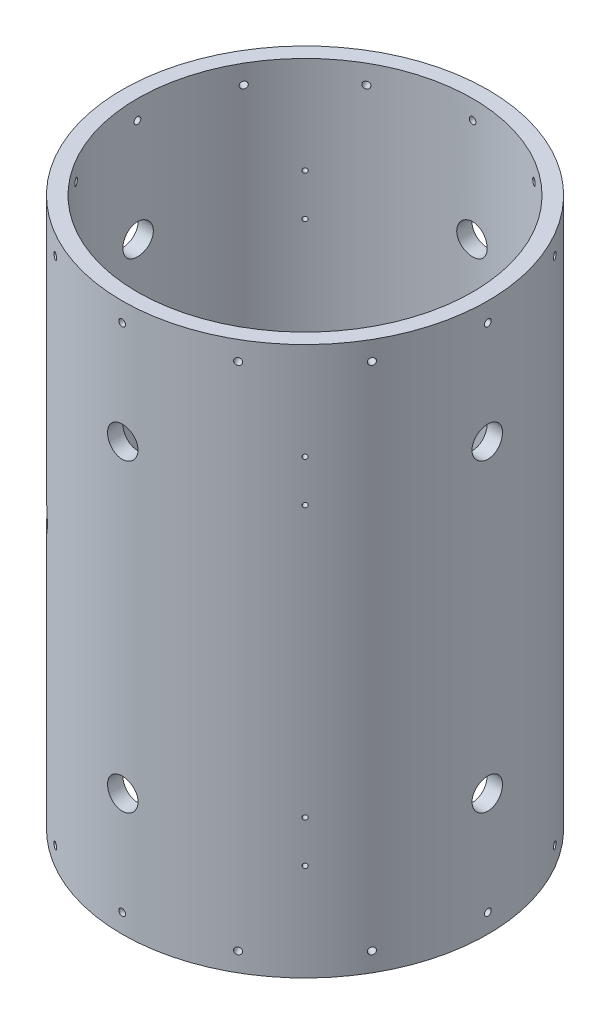
SolidWorks part; units mm, degrees
ref_plane "Front Plane" through (0, 0, 0) normal (0, 0, 1) x (1, 0, 0)
ref_plane "Top Plane" through (0, 0, 0) normal (0, 1, 0) x (1, 0, 0)
ref_plane "Right Plane" through (0, 0, 0) normal (1, 0, 0) x (0, 0, -1)
sketch "Sketch1" plane through (0, 0, 0) normal (0, 1, 0) x (1, 0, 0)
  circle A0 centre (0, 0) radius 152.4
  circle A1 centre (0, 0) radius 139.7
  dimension "D1" = 304.8
  dimension "D2" = 279.4
extrude "Boss-Extrude1" add sketch "Sketch1" along normal blind 457.2
ref_plane "Plane1" through (-152.4, 0, 0) normal (-1, 0, 0) x (0, 0, 1)
hole_wizard "#10 Clearance Hole1" positions "Sketch2" profile "Sketch3" hole size "#10" standard "ANSI Inch" end condition up to next
sketch "Sketch2" plane through (-152.4, 0, 0) normal (-1, 0, 0) x (0, 0, 1)
  line L0 (0, -167.64) -> (0, 167.64) construction
  line L1 (139.7, 457.2) -> (-139.7, 457.2) construction
  point P0 (0, 441.325)
  dimension "D1" = 15.875
sketch "Sketch3" plane through (-152.4, 441.325, 0) normal (0, 1, 0) x (0, 0, 1)
  line L0 (0, 0) -> (0, 343.2351)
  line L1 (0, 343.2351) -> (2.8067, 343.2351)
  line L2 (2.8067, 343.2351) -> (2.8067, 0)
  line L5 (2.8067, 0) -> (0, 0)
  line L11 (0, -6.35) -> (0, 107.95) construction
  dimension "Thru Hole Dia." = 5.6134
  dimension "Thru Hole Depth" = 343.2351
pattern_circular "CirPattern1" count 12 over 360 about axis through (0, 457.2, 0) along (0, -1, 0) of "#10 Clearance Hole1"
ref_plane "Plane2" through (0, 228.6, 0) normal (0, 1, 0) x (1, 0, 0)
mirror "Mirror1" about plane through (0, 228.6, 0) normal (0, 1, 0) of "CirPattern1"
ref_plane "Plane3" through (-107.7631, 0, -107.7631) normal (-0.7071, 0, -0.7071) x (0, -1, 0)
hole_wizard "Tap Drill for #10-24 Tap1" positions "Sketch5" profile "Sketch6" hole size "#10-24" standard "ANSI Inch" end condition up to next
sketch "Sketch5" plane through (-107.7631, 0, -107.7631) normal (-0.7071, 0, -0.7071) x (0, -1, 0)
  line L0 (-228.6, 167.64) -> (-228.6, -167.64) construction
  point P0 (-376.2375, 0)
  point P2 (-341.3125, 0)
  point P4 (-80.9625, 0)
  point P6 (-115.8875, 0)
  dimension "D1" = 112.7125
  dimension "D2" = 34.925
  dimension "D3" = 112.7125
  dimension "D4" = 34.925
sketch "Sketch6" plane through (-107.7631, 376.2375, -107.7631) normal (0, 1, 0) x (-0.7071, 0, 0.7071)
  line L0 (0, 0) -> (0, 304.8)
  line L1 (0, 304.8) -> (1.8986, 304.8)
  line L2 (1.8986, 304.8) -> (1.8986, 0)
  line L5 (1.8986, 0) -> (0, 0)
  line L11 (0, -6.35) -> (0, 107.95) construction
  dimension "Thru Hole Dia." = 3.7973
  dimension "Thru Hole Depth" = 304.8
pattern_circular "CirPattern2" count 2 over 360 about axis through (0, 457.2, 0) along (0, -1, 0) of "Tap Drill for #10-24 Tap1"
sketch "Sketch7" plane through (-152.4, 0, 0) normal (-1, 0, 0) x (0, 0, 1)
  line L0 (152.4, 457.2) -> (-152.4, 457.2) construction
  circle A0 centre (0, 355.6) radius 12.7
  dimension "D1" = 25.4
  dimension "D2" = 101.6
extrude "Cut-Extrude1" cut sketch "Sketch7" against normal up to next
pattern_circular "CirPattern3" count 4 over 360 about axis through (0, 457.2, 0) along (0, -1, 0) of "Cut-Extrude1"
mirror "Mirror2" about plane through (0, 228.6, 0) normal (0, 1, 0) of "CirPattern3", "Cut-Extrude1"
ref_plane "Plane4" through (-107.7631, 0, 107.7631) normal (-0.7071, 0, 0.7071) x (0, -1, 0)
sketch "Sketch8" plane through (-107.7631, 0, 107.7631) normal (-0.7071, 0, 0.7071) x (0, -1, 0)
  line L0 (-228.6, 167.64) -> (-228.6, -167.64) construction
  circle A0 centre (-228.6, 0) radius 12.7
  dimension "D1" = 25.4
extrude "Cut-Extrude2" cut sketch "Sketch8" against normal up to next
equation "\"D3@Sketch4\"=\"D2@Sketch4\""
